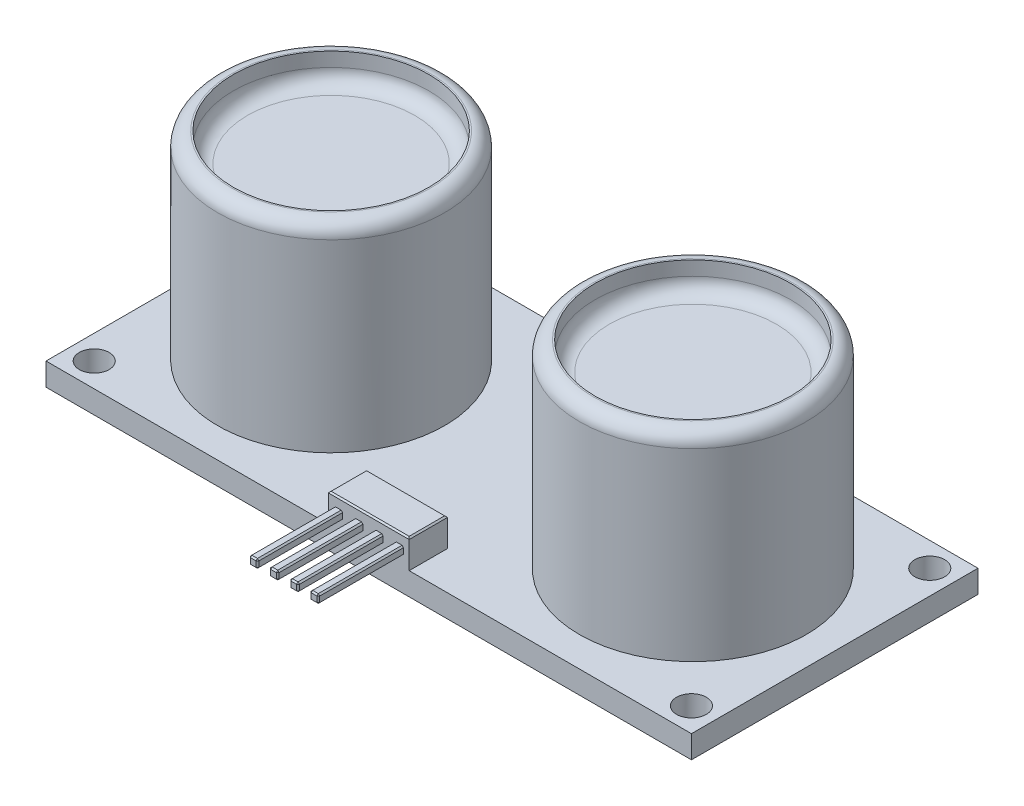
SolidWorks part; units mm, degrees
ref_plane "Front Plane" through (0, 0, 0) normal (0, 0, 1) x (1, 0, 0)
ref_plane "Top Plane" through (0, 0, 0) normal (0, 1, 0) x (1, 0, 0)
ref_plane "Right Plane" through (0, 0, 0) normal (1, 0, 0) x (0, 0, -1)
sketch "Sketch1" plane through (0, 0, 0) normal (0, 1, 0) x (1, 0, 0)
  line L0 (22.75, 20.2) -> (22.75, 0) construction
  line L1 (0, 0) -> (45.5, 0)
  line L2 (0, 0) -> (0, 20.2)
  line L3 (0, 20.2) -> (45.5, 20.2)
  line L4 (45.5, 0) -> (45.5, 20.2)
  dimension "D1" = 20.2
  dimension "D2" = 45.5
extrude "Boss-Extrude1" add sketch "Sketch1" along normal blind 1.6
sketch "Sketch2" plane through (0, 1.6, 0) normal (0, 1, 0) x (1, 0, 0)
  line L0 (0, 10.1) -> (45.5, 10.1) construction
  line L1 (0, 20.2) -> (0, 0) construction
  line L2 (45.5, 0) -> (45.5, 20.2) construction
  circle A0 centre (10, 10.1) radius 8
  dimension "D1" = 16
  dimension "D2" = 10
extrude "Boss-Extrude2" add sketch "Sketch2" along normal blind 14
sketch "Sketch3" plane through (0, 15.6, 0) normal (0, 1, 0) x (1, 0, 0)
  circle A0 centre (10, 10.1) radius 6.894
extrude "Cut-Extrude1" cut sketch "Sketch3" against normal blind 2
fillet "Fillet1" radius 1 1 edges at (10, 15.6, -2.1)
fillet "Fillet2" radius 1 1 edges at (10, 13.6, -3.206)
ref_axis "Axis1" through (22.75, 0, -20.2) along (0, 0, 1)
ref_plane "Plane1" through (22.75, 0, 0) normal (1, 0, 0) x (0, 0, -1)
mirror "Mirror1" about plane through (22.75, 0, 0) normal (1, 0, 0) of "Fillet2", "Fillet1", "Cut-Extrude1", "Boss-Extrude2"
sketch "Sketch4" plane through (0, 1.6, 0) normal (0, 1, 0) x (1, 0, 0)
  line L0 (22.75, 0) -> (19.9, 0)
  line L1 (0, 0) -> (45.5, 0) construction
  line L2 (22.75, 0) -> (25.6, 0)
  line L3 (19.9, 0) -> (19.9, 2.7)
  line L4 (19.9, 2.7) -> (25.6, 2.7)
  line L5 (25.6, 2.7) -> (25.6, 0)
  dimension "D1" = 2.85
  dimension "D2" = 2.85
  dimension "D3" = 2.7
extrude "Boss-Extrude3" add sketch "Sketch4" along normal blind 2
sketch "Sketch5" plane through (0, 0, 0) normal (0, 0, 1) x (1, 0, 0)
  line L0 (19.9, 2.6) -> (25.6, 2.6) construction
  line L1 (19.9, 3.6) -> (19.9, 1.6) construction
  line L2 (25.6, 3.6) -> (25.6, 1.6) construction
  line L3 (21.7362, 2.3) -> (22.3362, 2.9) construction
  line L4 (20.3062, 2.3) -> (20.9062, 2.3)
  line L5 (20.3062, 2.3) -> (20.3062, 2.9)
  line L6 (20.3062, 2.9) -> (20.9062, 2.9)
  line L7 (20.9062, 2.3) -> (20.9062, 2.9)
  line L8 (20.3062, 2.3) -> (20.9062, 2.9) construction
  line L9 (20.3062, 2.9) -> (20.9062, 2.3) construction
  line L10 (21.7362, 2.9) -> (22.3362, 2.3) construction
  line L11 (21.7362, 2.3) -> (21.7362, 2.9)
  line L12 (21.7362, 2.3) -> (22.3362, 2.3)
  line L13 (22.3362, 2.3) -> (22.3362, 2.9)
  line L14 (21.7362, 2.9) -> (22.3362, 2.9)
  line L15 (23.1662, 2.3) -> (23.7662, 2.9) construction
  line L16 (23.1662, 2.9) -> (23.7662, 2.3) construction
  line L17 (23.1662, 2.3) -> (23.1662, 2.9)
  line L18 (23.1662, 2.3) -> (23.7662, 2.3)
  line L19 (23.7662, 2.3) -> (23.7662, 2.9)
  line L20 (23.1662, 2.9) -> (23.7662, 2.9)
  line L21 (24.5962, 2.3) -> (25.1962, 2.9) construction
  line L22 (24.5962, 2.9) -> (25.1962, 2.3) construction
  line L23 (24.5962, 2.3) -> (24.5962, 2.9)
  line L24 (24.5962, 2.3) -> (25.1962, 2.3)
  line L25 (25.1962, 2.3) -> (25.1962, 2.9)
  line L26 (24.5962, 2.9) -> (25.1962, 2.9)
  point P6 (20.6062, 2.6)
  point P12 (22.0362, 2.6)
  point P17 (23.4662, 2.6)
  point P22 (24.8962, 2.6)
  dimension "D1" = 0.6
  dimension "D2" = 4
extrude "Boss-Extrude4" add sketch "Sketch5" along normal blind 6
chamfer "Chamfer1" distance 0.1 angle 45 32 edges at (25.1962, 2.6, 6) (25.1962, 2.3, 3) (24.8962, 2.3, 6) (24.5962, 2.3, 3) (24.5962, 2.6, 6) (25.1962, 2.9, 3) (24.8962, 2.9, 6) (24.5962, 2.9, 3) (23.7662, 2.6, 6) (23.7662, 2.3, 3) (23.4662, 2.3, 6) (23.1662, 2.3, 3) (23.1662, 2.6, 6) (23.1662, 2.9, 3) (23.4662, 2.9, 6) (23.7662, 2.9, 3) (22.3362, 2.6, 6) (22.3362, 2.3, 3) (22.0362, 2.3, 6) (21.7362, 2.3, 3) (21.7362, 2.6, 6) (22.3362, 2.9, 3) (22.0362, 2.9, 6) (21.7362, 2.9, 3) (20.6062, 2.3, 6) (20.3062, 2.3, 3) (20.3062, 2.6, 6) (20.3062, 2.9, 3) (20.6062, 2.9, 6) (20.9062, 2.3, 3) (20.9062, 2.6, 6) (20.9062, 2.9, 3)
chamfer "Chamfer2" distance 0.1 angle 45 4 edges at (19.9, 3.6, -1.35) (22.75, 3.6, -2.7) (25.6, 3.6, -1.35) (22.75, 3.6, 0)
sketch "Sketch6" plane through (0, 1.6, 0) normal (0, 1, 0) x (1, 0, 0)
  line L0 (22.75, 20.2) -> (1.7, 20.2) construction
  line L1 (45.5, 20.2) -> (0, 20.2) construction
  line L2 (22.75, 20.2) -> (42.75, 20.2) construction
  line L3 (1.7, 20.2) -> (1.7, 18.5) construction
  line L4 (1.7, 0) -> (1.7, 1.7) construction
  line L5 (0, 0) -> (19.9, 0) construction
  line L6 (0, 20.2) -> (0, 0) construction
  line L7 (45.5, 0) -> (45.5, 20.2) construction
  circle A0 centre (1.7, 18.5) radius 1.05
  circle A1 centre (1.7, 1.7) radius 1.05
  circle A2 centre (43.8, 1.7) radius 1.05
  circle A3 centre (43.8, 18.5) radius 1.05
  dimension "D5" = 2.1
  dimension "D6" = 2.1
  dimension "D7" = 2.1
  dimension "D8" = 2.1
  dimension "D1" = 1.7
  dimension "D2" = 1.7
  dimension "D3" = 1.7
  dimension "D4" = 1.7
extrude "Cut-Extrude2" cut sketch "Sketch6" against normal up to next
sketch "Sketch7" plane through (0, 1.6, 0) normal (0, 1, 0) x (1, 0, 0)
  line L0 (1.7, 18.5) -> (43.8, 18.5) construction
  line L1 (22.75, 18.5) -> (22.75, 7.4192) construction
  point P6 (0, 0)
ref_axis "Axis2" through (22.75, 1.6, -18.5) along (0, 0, 1)
